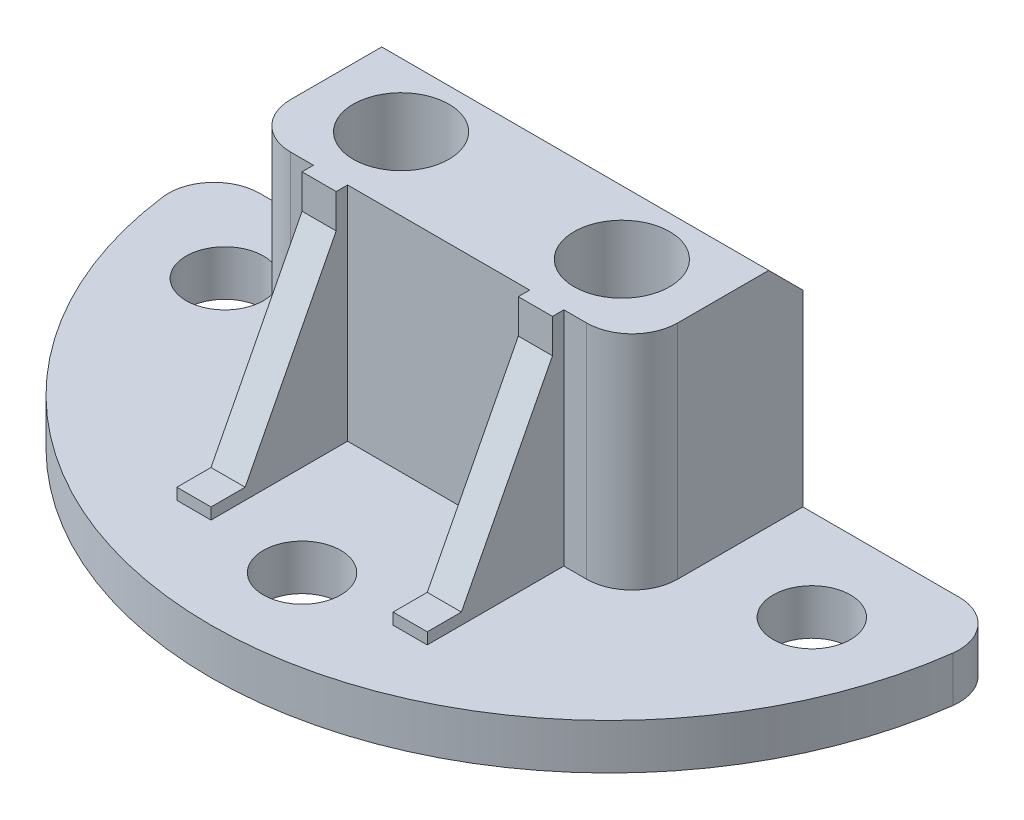
SolidWorks part; units mm, degrees
ref_plane "Front Plane" through (0, 0, 0) normal (0, 0, 1) x (1, 0, 0)
ref_plane "Top Plane" through (0, 0, 0) normal (0, 1, 0) x (1, 0, 0)
ref_plane "Right Plane" through (0, 0, 0) normal (1, 0, 0) x (0, 0, -1)
sketch "Sketch1" plane through (0, 0, 0) normal (0, 1, 0) x (1, 0, 0)
  line L0 (-17.5, 0) -> (17.5, 0)
  line L1 (-4.85, -4.3) -> (4.85, -4.3) construction
  line L2 (-12.8938, -4) -> (12.8938, -4) construction
  line L3 (-8.5, 7.5) -> (8.5, 7.5)
  line L4 (-8.5, 7.5) -> (-8.5, -7.5)
  line L5 (-8.5, -7.5) -> (8.5, -7.5)
  line L6 (8.5, 7.5) -> (8.5, -7.5)
  line L7 (-8.5, 7.5) -> (8.5, -7.5) construction
  line L8 (-8.5, -7.5) -> (8.5, 7.5) construction
  line L9 (12.8938, -4) -> (0, -13.5) construction
  line L10 (0, -13.5) -> (-12.8938, -4) construction
  circle A0 centre (0, 0) radius 17.5
  circle A1 centre (-4.85, -4.3) radius 2.1
  circle A2 centre (4.85, -4.3) radius 2.1
  circle A3 centre (12.8938, -4) radius 1.7
  circle A4 centre (0, -13.5) radius 1.7
  circle A5 centre (-12.8938, -4) radius 1.7
  circle A6 centre (0, 0) radius 13.5
  point P6 (0, 0)
  point P10 (0, -4.3)
  dimension "D3" = 35
  dimension "D6" = 4.2
  dimension "D7" = 3.4
  dimension "D8" = 4
  dimension "D1" = 9.7
  dimension "D2" = 4.3
  dimension "D4" = 17
  dimension "D5" = 15
  dimension "D9" = 4
extrude "Boss-Extrude1" add sketch "Sketch1" along normal blind 2 contours A4 A6 A3 L0 L6 L5 L4 A5 | A6 A4 A5 L0 A0 A3 region at (13.1482, 0, 1.1521) region at (15.5, 0, 0.3913)
extrude "Boss-Extrude2" add sketch "Sketch1<3>" along normal blind 11.75 contours L6 L0 L4 L5 A2 A1 | A1 | A2 region at (0, 0, 3.5973) region at (-4.85, 0, 4.3) region at (4.85, 0, 4.3)
sketch "Sketch1<3>" plane through (0, 0, 0) normal (0, 1, 0) x (1, 0, 0) same geometry as "Sketch1"
fillet "Fillet1" radius 2 4 edges at (-17.5, 1, 0) (-8.5, 6.875, 7.5) (8.5, 6.875, 7.5) (17.5, 1, 0)
chamfer "Chamfer1" distance 1.5 angle 45 1 edges at (0, 11.75, 0)
sketch "Sketch2" plane through (0, 0, 7.5) normal (0, 0, 1) x (1, 0, 0)
  line L0 (17.3537, 2) -> (-17.3537, 2) construction
  line L1 (-5.5, 11.75) -> (-4, 11.75)
  line L2 (-5.5, 11.75) -> (-5.5, 2)
  line L3 (-5.5, 2) -> (-4, 2)
  line L4 (-4, 11.75) -> (-4, 2)
  line L5 (-6.5, 2) -> (6.5, 2) construction
  line L6 (4, 11.75) -> (5.5, 11.75)
  line L7 (4, 11.75) -> (4, 2)
  line L8 (4, 2) -> (5.5, 2)
  line L9 (5.5, 11.75) -> (5.5, 2)
  line L10 (-4, 6.875) -> (4, 6.875) construction
  line L11 (-6.5, 11.75) -> (6.5, 11.75) construction
  point P14 (0, 6.875)
  dimension "D2" = 8
  dimension "D3" = 1.5
extrude "Boss-Extrude3" add sketch "Sketch2" along normal blind 6
sketch "Sketch3" plane through (5.5, 0, 0) normal (1, 0, 0) x (0, 0, -1)
  line L0 (-8, 11.75) -> (-8, 10.25)
  line L1 (-13.5, 11.75) -> (-7.5, 11.75) construction
  line L2 (-8, 10.25) -> (-12, 2.5)
  line L3 (-12, 2.5) -> (-13.5, 2.5)
  line L4 (-13.5, 2) -> (-13.5, 11.75) construction
  line L5 (-13.5, 2.5) -> (-13.5, 2)
  line L6 (-13.5, 2) -> (-7.5, 2)
  line L7 (-7.5, 2) -> (-7.5, 11.75)
  line L8 (-7.5, 11.75) -> (-8, 11.75)
  line L9 (-13.5, 2.5) -> (-13.5, 11.75)
  line L10 (-13.5, 11.75) -> (-8, 11.75)
  line M6 (-7.5, 11.75) -> (-13.5, 11.75)
  line M7 (-13.5, 11.75) -> (-13.5, 2)
  dimension "D1" = 1.5
  dimension "D2" = 0.5
extrude "Cut-Extrude1" cut sketch "Sketch3" against normal through all contours L3 L2 L0 M6 M7 region at (5.5, 8.0196, 11.3707)
extrude "Cut-Extrude2" cut sketch "Sketch1<4>" against normal blind 5 from surface contours A1 | A2 starting at face at (0, 11.75, 6.5592)
sketch "Sketch1<4>" plane through (0, 0, 0) normal (0, 1, 0) x (1, 0, 0) same geometry as "Sketch1"
